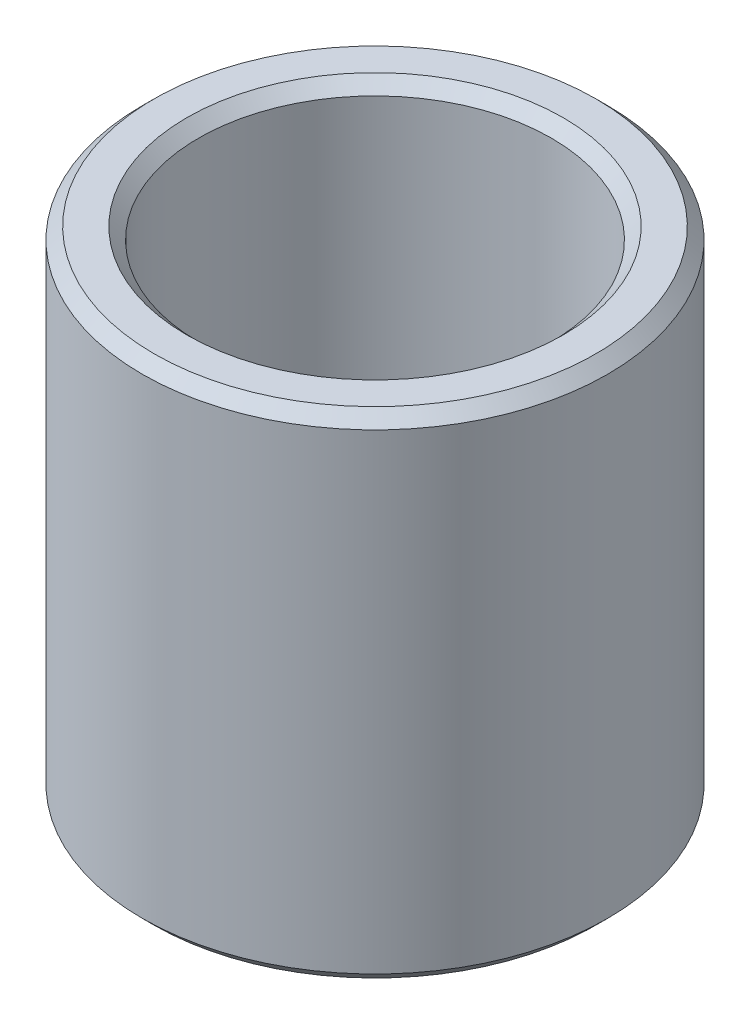
SolidWorks part; units mm, degrees
ref_plane "Front Plane" through (0, 0, 0) normal (0, 0, 1) x (1, 0, 0)
ref_plane "Top Plane" through (0, 0, 0) normal (0, 1, 0) x (1, 0, 0)
ref_plane "Right Plane" through (0, 0, 0) normal (1, 0, 0) x (0, 0, -1)
sketch "Sketch1" plane through (0, 0, 0) normal (0, 1, 0) x (1, 0, 0)
  circle A0 centre (0, 0) radius 37.5
  dimension "SLEEVE_OD" = 75
extrude "Boss-Extrude1" add sketch "Sketch1" along normal blind 79.7517
sketch "Sketch2" plane through (0, 0, 0) normal (0, 1, 0) x (1, 0, 0)
  circle A0 centre (0, 0) radius 28.4323
  dimension "BORE_D" = 56.8647
extrude "Cut-Extrude1" cut sketch "Sketch2" along normal through all
chamfer "Chamfer1" distance 1.9017 angle 45 4 edges at (0, 79.7517, 28.4323) (0, 0, 28.4323) (0, 0, 37.5) (0, 79.7517, 37.5)
